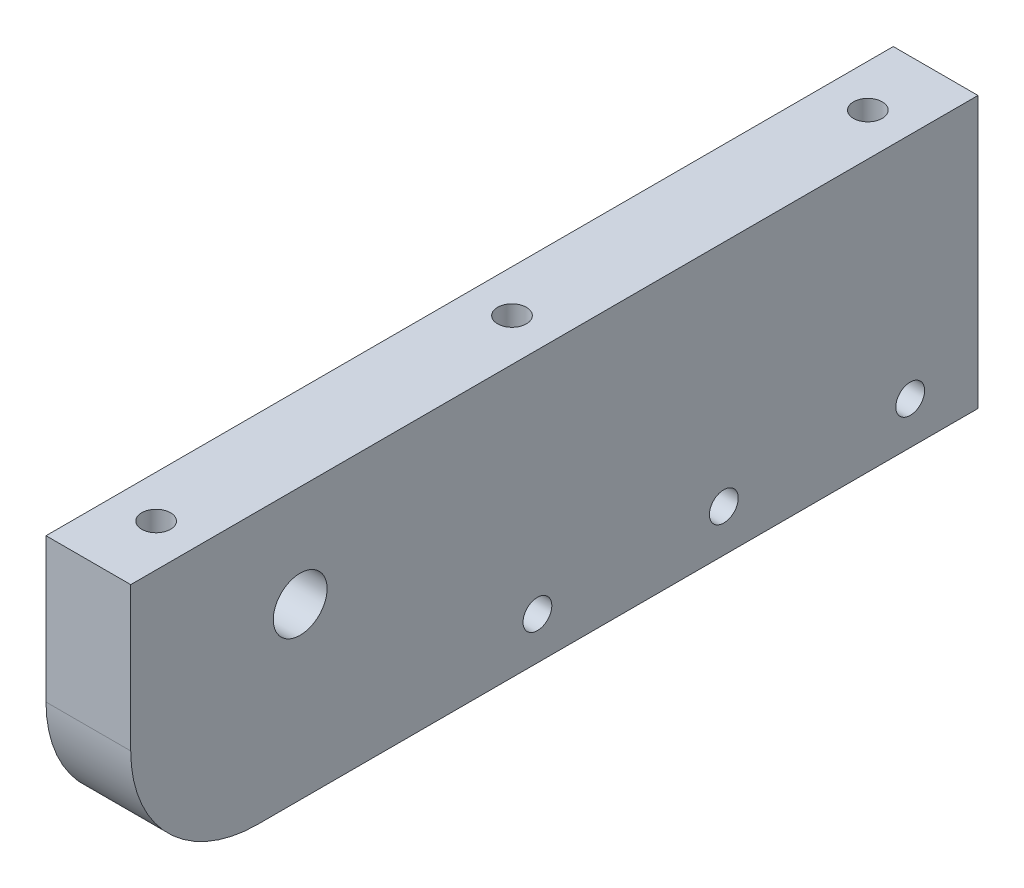
SolidWorks part; units mm, degrees
material "Plain Carbon Steel"
ref_plane "Front Plane" through (0, 0, 0) normal (0, 0, 1) x (1, 0, 0)
ref_plane "Top Plane" through (0, 0, 0) normal (0, 1, 0) x (1, 0, 0)
ref_plane "Right Plane" through (0, 0, 0) normal (1, 0, 0) x (0, 0, -1)
sketch "Sketch1" plane through (0, 0, 0) normal (1, 0, 0) x (0, 0, -1)
  line L1 (-50, -16) -> (50, -16)
  line L2 (-50, -16) -> (-50, 16)
  line L3 (-50, 16) -> (50, 16)
  line L4 (50, -16) -> (50, 16)
  line L5 (-50, -16) -> (50, 16) construction
  line L6 (-50, 16) -> (50, -16) construction
  circle A1 centre (-30, 4) radius 3.175
  point P0 (0, 0)
  dimension "D3" = 6.35
  dimension "D1" = 32
  dimension "D2" = 100
  dimension "D4" = 12
  dimension "D5" = 20
extrude "Boss-Extrude1" add sketch "Sketch1" along normal blind 10 contours L1 L4 L3 L2 region at (0, -0.04, -0.2999)
fillet "Fillet1" radius 15 1 edges at (5, -16, 50)
hole_wizard "CBORE for M3 SHCS" positions "Sketch2" profile "Sketch3" counterbore size "M3" standard "ANSI Metric"
sketch "Sketch2" plane through (-616.2935, 26, -1323.2827) normal (0, 1, 0) x (1, 0, 0)
  line L3 (621.2935, -1281.2827) -> (621.2935, -1365.2827) construction
  line L5 (731.2935, -1281.2827) -> (731.2935, -1343.2827) construction
  circle A0 centre (731.2935, -1281.2827) radius 2.243
  circle A1 centre (731.2935, -1343.2827) radius 2.2384
  circle A3 centre (621.2935, -1281.2827) radius 2.3325
  circle A4 centre (621.2935, -1365.2827) radius 1.7576
  circle A5 centre (621.2935, -1323.2827) radius 1.8624
  circle A6 centre (731.2935, -1312.2827) radius 2.0271
  point P1 (731.2935, -1281.2827)
  point P8 (731.2935, -1343.2827)
  point P15 (621.2935, -1281.2827)
  point P17 (621.2935, -1365.2827)
  point P19 (621.2935, -1323.2827)
  point P27 (731.2935, -1312.2827)
sketch "Sketch3" plane through (115, 26, -42) normal (1, 0, 0) x (0, 0, 1)
  line L0 (0, 0) -> (0, 24.0215)
  line L1 (0, 24.0215) -> (1.7, 23)
  line L2 (1.7, 23) -> (1.7, 3)
  line L3 (1.7, 3) -> (3.25, 3)
  line L4 (3.25, 3) -> (3.25, 0)
  line L5 (3.25, 0) -> (0, 0)
  line L6 (0, 24.0215) -> (-1.7, 23) construction
  line L7 (0, -6.35) -> (0, 107.95) construction
  dimension "Hole Dia." = 3.4
  dimension "Hole Depth" = 23
  dimension "C'Bore Dia." = 6.5
  dimension "C'Bore Depth" = 3
  dimension "Drill Angle" = 118
hole_wizard "CBORE for M3 SHCS1" positions "Sketch4" profile "Sketch5" counterbore size "M3" standard "ANSI Metric"
sketch "Sketch4" plane through (0, -904.0121, -1323.2827) normal (-1, 0, 0) x (0, 0, 1)
  line L0 (1281.2827, 893.0121) -> (1325.2827, 893.0121) construction
  point P0 (1281.2827, 893.0121)
  point P1 (1325.2827, 893.0121)
  point P4 (1303.2827, 893.0121)
sketch "Sketch5" plane through (0, -11, -42) normal (0, 1, 0) x (0, 0, 1)
  line L0 (0, 0) -> (0, 24.0215)
  line L1 (0, 24.0215) -> (1.7, 23)
  line L2 (1.7, 23) -> (1.7, 3)
  line L3 (1.7, 3) -> (3.25, 3)
  line L4 (3.25, 3) -> (3.25, 0)
  line L5 (3.25, 0) -> (0, 0)
  line L6 (0, 24.0215) -> (-1.7, 23) construction
  line L7 (0, -6.35) -> (0, 107.95) construction
  dimension "Hole Dia." = 3.4
  dimension "Hole Depth" = 23
  dimension "C'Bore Dia." = 6.5
  dimension "C'Bore Depth" = 3
  dimension "Drill Angle" = 118
